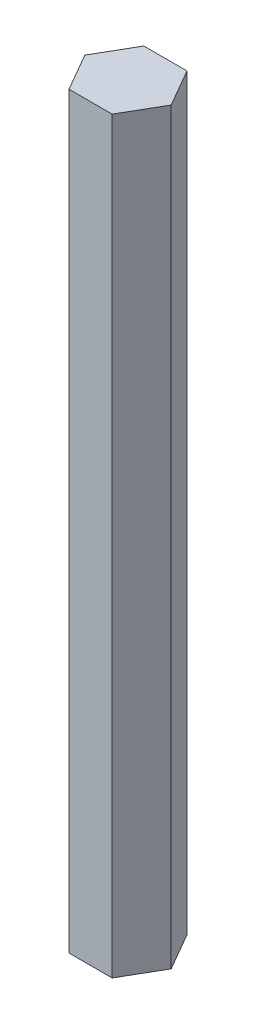
SolidWorks part; units mm, degrees
ref_plane "Front Plane" through (0, 0, 0) normal (0, 0, 1) x (1, 0, 0)
ref_plane "Top Plane" through (0, 0, 0) normal (0, 1, 0) x (1, 0, 0)
ref_plane "Right Plane" through (0, 0, 0) normal (1, 0, 0) x (0, 0, -1)
sketch "Sketch1" plane through (0, 0, 0) normal (0, 1, 0) x (1, 0, 0)
  line L1 (7.3323, 0) -> (3.6662, 6.35)
  line L2 (3.6662, 6.35) -> (-3.6662, 6.35)
  line L3 (-3.6662, 6.35) -> (-7.3323, 0)
  line L4 (-7.3323, 0) -> (-3.6662, -6.35)
  line L5 (-3.6662, -6.35) -> (3.6662, -6.35)
  line L6 (3.6662, -6.35) -> (7.3323, 0)
  circle A0 centre (0, 0) radius 6.35 construction
  dimension "D1" = 12.7
extrude "Boss-Extrude1" add sketch "Sketch1" along normal mid plane 127
ref_axis "Center Axis" through (0, 69.85, 0) along (0, -1, 0)
ref_plane "Mid Plane" through (0, 0, 0) normal (0, 1, 0) x (1, 0, 0)
ref_point "Center"
